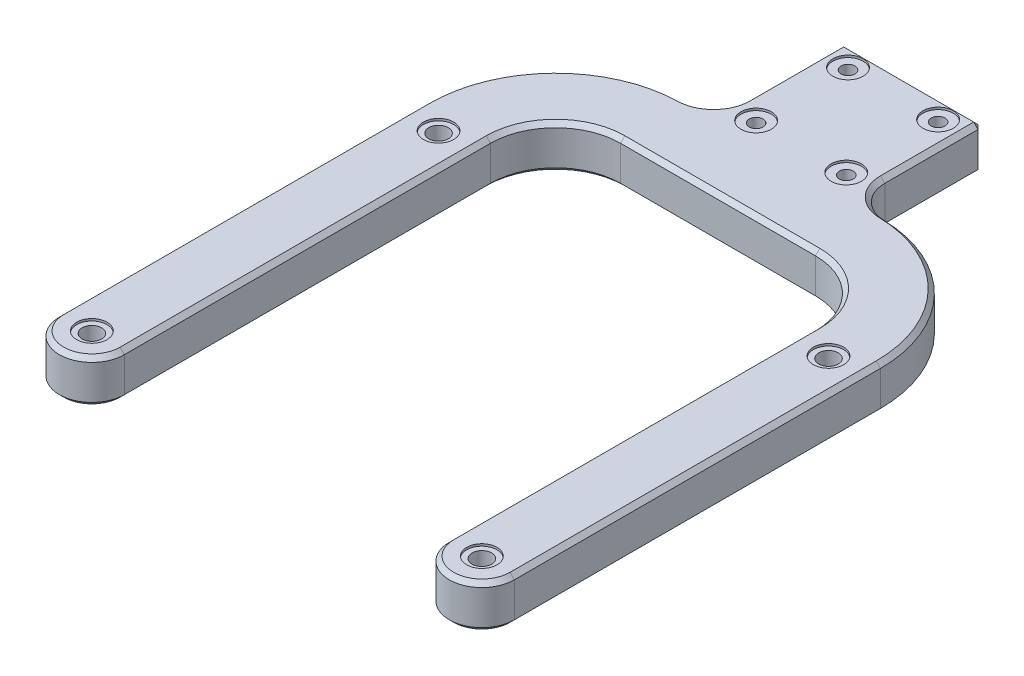
SolidWorks part; units mm, degrees
material "ABS PC"
ref_plane "Front Plane" through (0, 0, 0) normal (0, 0, 1) x (1, 0, 0)
ref_plane "Top Plane" through (0, 0, 0) normal (0, 1, 0) x (1, 0, 0)
ref_plane "Right Plane" through (0, 0, 0) normal (1, 0, 0) x (0, 0, -1)
sketch "Sketch1" plane through (0, 0, 0) normal (0, 1, 0) x (1, 0, 0)
  line L0 (22.5, 57.25) -> (0, 57.25)
  line L1 (0, 57.25) -> (0, 102.25)
  line L2 (37.5, 42.25) -> (37.5, -42.25)
  line L7 (16, 102.25) -> (0, 102.25)
  line L8 (0, 0) -> (0, 57.25) construction
  line L9 (16, 102.25) -> (16, 72.25)
  line L13 (16, 72.25) -> (22.5, 72.25)
  line L14 (52.5, 42.25) -> (52.5, -42.25)
  arc A4 (22.5, 57.25) -> (37.5, 42.25) centre (22.5, 42.25) cw
  arc A6 (22.5, 72.25) -> (52.5, 42.25) centre (22.5, 42.25) cw
  circle A7 centre (10.4, 97.65) radius 1.6
  circle A8 centre (10.4, 76.45) radius 1.6
  arc A9 (37.5, -42.25) -> (52.5, -42.25) centre (45, -42.25) ccw
  circle A10 centre (45, 37.75) radius 2.25
  circle A11 centre (45, -42.25) radius 2.25
  point P10 (37.5, 0)
  dimension "D7" = 80
  dimension "D8" = 30
  dimension "D9" = 15
  dimension "D10" = 3.2
  dimension "D11" = 18
  dimension "D12" = 3
  dimension "D13" = 4
  dimension "D6" = 107
  dimension "D14" = 4.5
  dimension "D1" = 15
  dimension "D2" = 15
  dimension "D3" = 30
  dimension "D4" = 32
  dimension "D5" = 75
extrude "Boss-Extrude1" add sketch "Sketch1" along normal blind 10
sketch "Sketch4" plane through (0, 10, 0) normal (0, 1, 0) x (1, 0, 0)
  circle A0 centre (10.4, 97.65) radius 3.5
  circle A1 centre (10.4, 76.45) radius 3.5
  circle A2 centre (45, 37.75) radius 3.5
  circle A3 centre (45, -42.25) radius 3.5
  dimension "D1" = 7
extrude "Cut-Extrude1" cut sketch "Sketch4" against normal blind 0.5
fillet "Fillet1" radius 7.5 1 edges at (16, 5, -72.25)
chamfer "Chamfer1" distance 1 angle 45 19 edges at (11.25, 0, -57.25) (33.1066, 0, -52.8566) (37.5, 0, 0) (52.5, 0, 0) (43.9942, 0, -63.1784) (16, 0, -90.9933) (8, 0, -102.25) (11.25, 10, -57.25) (33.1066, 10, -52.8566) (37.5, 10, 0) (52.5, 10, 0) (43.9942, 10, -63.1784) (16, 10, -90.9933) (8, 10, -102.25) (18.1265, 0, -74.5046) (18.1265, 10, -74.5046) (16, 5, -102.25) (45, 0, 49.75) (45, 10, 49.75)
sketch "Sketch5" plane through (0, 0, 0) normal (0, -1, 0) x (1, 0, 0)
  circle A0 centre (45, -37.75) radius 2.25 construction
  circle A1 centre (45, 42.25) radius 2.25 construction
  circle A2 centre (45, -37.75) radius 2.25
  circle A3 centre (45, 42.25) radius 2.25
extrude "Boss-Extrude2" add sketch "Sketch5" against normal offset from surface (4 mm away) 6 up to face at (10.4, 10, -94.15)
mirror "Mirror1" about plane through (0, 10, -57.25) normal (1, 0, 0) of bodies 104 101
